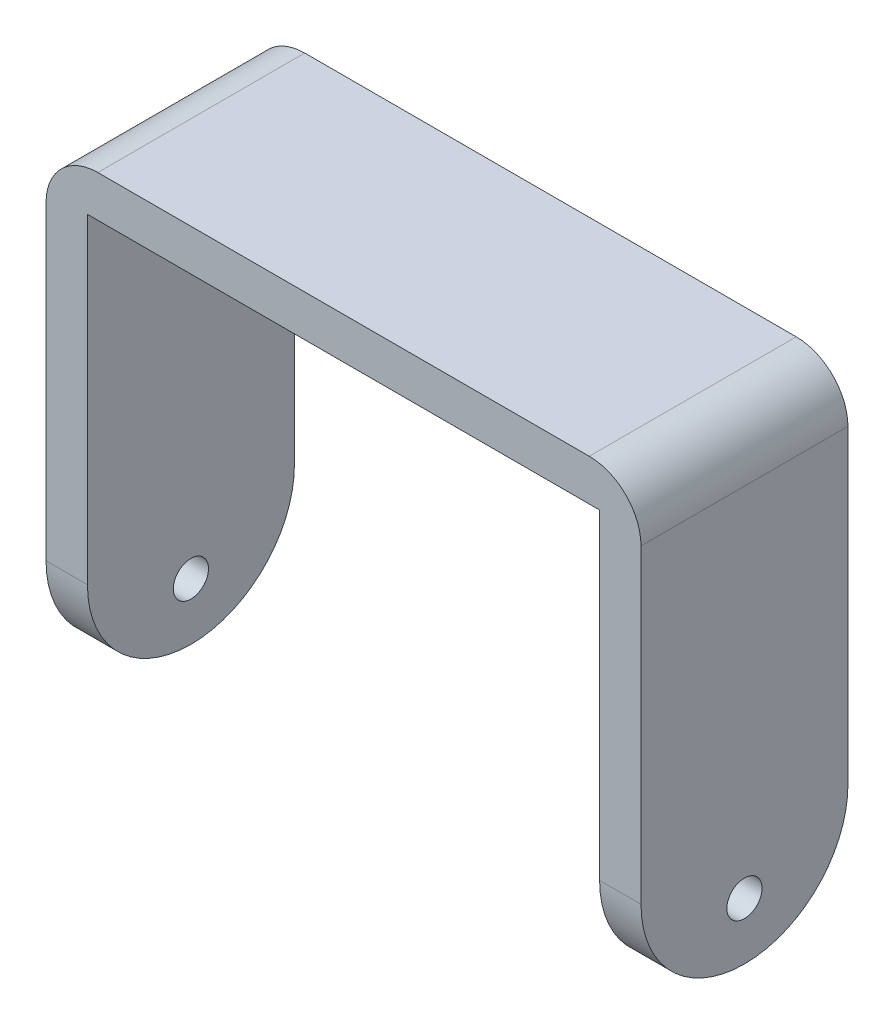
SolidWorks part; units mm, degrees
ref_plane "Plan de face" through (0, 0, 0) normal (0, 0, 1) x (1, 0, 0)
ref_plane "Plan de dessus" through (0, 0, 0) normal (0, 1, 0) x (1, 0, 0)
ref_plane "Plan de droite" through (0, 0, 0) normal (1, 0, 0) x (0, 0, -1)
sketch "Esquisse1" plane through (0, 0, 0) normal (0, 0, 1) x (1, 0, 0)
  line L0 (0, 0) -> (4, 0)
  line L1 (0, 0) -> (57.5, 0) construction
  line L2 (0, 0) -> (0, 45) construction
  line L3 (0, 45) -> (57.5, 45) construction
  line L4 (57.5, 0) -> (57.5, 45) construction
  line L5 (4, 0) -> (4, 41)
  line L6 (4, 41) -> (53.5, 41)
  line L7 (53.5, 41) -> (53.5, 0)
  line L8 (53.5, 0) -> (57.5, 0)
  line L9 (57.5, 0) -> (57.5, 45)
  line L10 (57.5, 45) -> (0, 45)
  line L11 (0, 45) -> (0, 0)
  point P10 (28.75, 41)
  point P11 (28.75, 0)
  dimension "D1" = 45
  dimension "D2" = 57.5
  dimension "D3" = 49.5
  dimension "D4" = 4
extrude "Boss.-Extru.1" add sketch "Esquisse1" along normal blind 20
sketch "Esquisse2" plane through (57.5, 0, 0) normal (1, 0, 0) x (0, 0, -1)
  line L4 (-10, 0) -> (-10, 10.519) construction
  line L5 (-20, 0) -> (0, 0) construction
  circle A0 centre (-10, 5.5) radius 1.5
  dimension "D1" = 3
  dimension "D2" = 5.5
extrude "Enlèv. mat.-Extru.1" cut sketch "Esquisse2" against normal up to surface (57.5 mm away) up to face at (0, 22.5, 10)
hole_wizard "Dégagement M31" positions "Esquisse3" profile "Esquisse5" hole size "M3" standard "ISO"
sketch "Esquisse3" plane through (57.5, 0, 0) normal (1, 0, 0) x (0, 0, -1)
  point P0 (-10, 5.5)
sketch "Esquisse5" plane through (57.5, 5.5, 10) normal (0, 1, 0) x (0, 0, -1)
  line L0 (0, 0) -> (0, 58.5215)
  line L1 (0, 58.5215) -> (1.7, 57.5)
  line L2 (1.7, 57.5) -> (1.7, 0)
  line L5 (1.7, 0) -> (0, 0)
  line L10 (0, 58.5215) -> (-1.7, 57.5) construction
  line L11 (0, -6.35) -> (0, 107.95) construction
  dimension "Diamètre du perçage" = 3.4
  dimension "Profondeur du perçage" = 57.5
  dimension "Angle de pointe" = 118
fillet "Congé1" radius 10 4 edges at (55.5, 0, 0) (55.5, 0, 20) (2, 0, 0) (2, 0, 20)
fillet "Congé2" radius 5 2 edges at (0, 45, 10) (57.5, 45, 10)
